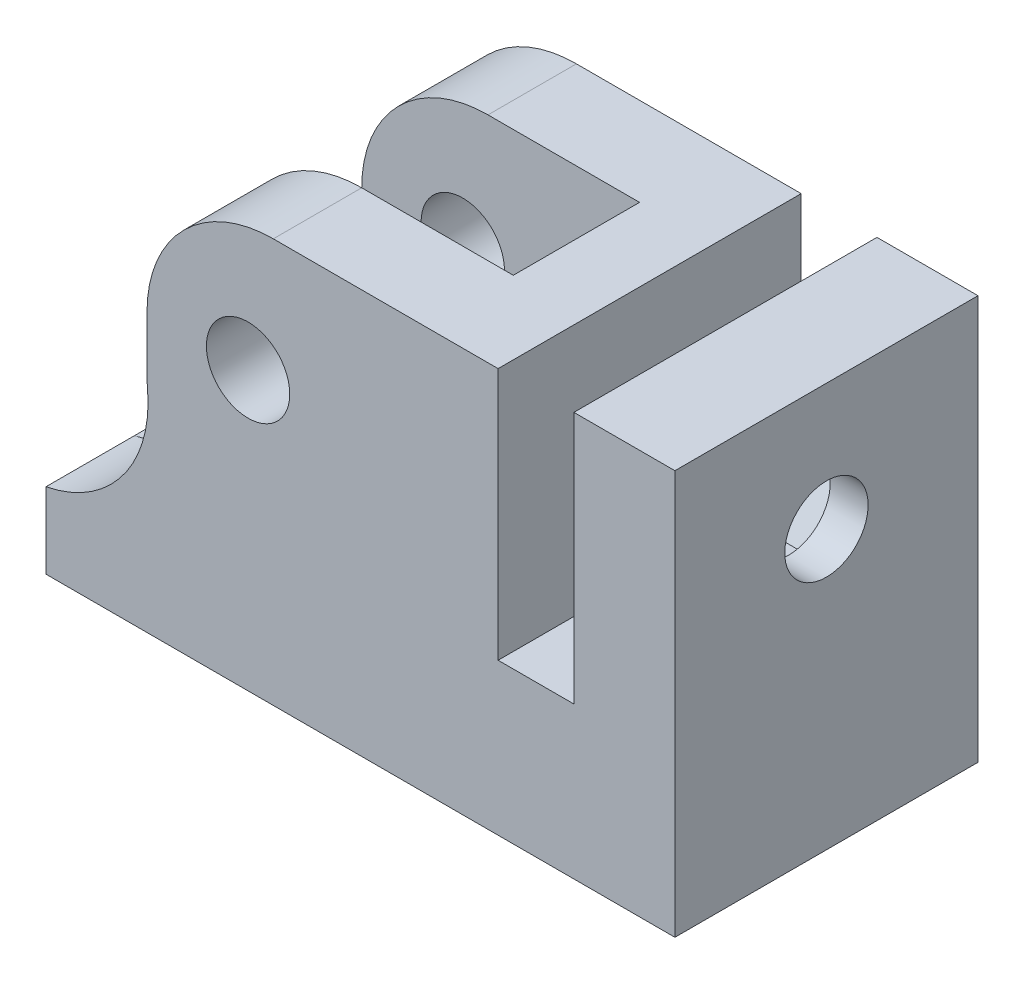
SolidWorks part; units mm, degrees
ref_plane "Plano frontal" through (0, 0, 0) normal (0, 0, 1) x (1, 0, 0)
ref_plane "Plano superior" through (0, 0, 0) normal (0, 1, 0) x (1, 0, 0)
ref_plane "Plano direito" through (0, 0, 0) normal (1, 0, 0) x (0, 0, -1)
sketch "Esboço1" plane through (0, 0, 0) normal (0, 0, 1) x (1, 0, 0)
  line L0 (0, 0) -> (-13.9, 0)
  line L1 (-13.9, 0) -> (-13.9, -10)
  line L3 (-13.9, -10) -> (-4, -16)
  line L4 (-4, -16) -> (7, -16)
  line L5 (7, -16) -> (7, 0)
  line L6 (7, 0) -> (3, 0)
  line L7 (3, 0) -> (3, -10)
  line L8 (3, -10) -> (0, -10)
  line L9 (0, -10) -> (0, 0)
  circle A0 centre (-9.9, -5) radius 1.65
  circle A1 centre (-9.9, -5) radius 6 construction
  point P3 (1.5, -10)
  point P5 (0, -5)
  dimension "D8" = 3.3
  dimension "D9" = 12
  dimension "D2" = 4
  dimension "D3" = 10
  dimension "D4" = 3
  dimension "D5" = 4
  dimension "D6" = 6
  dimension "D7" = 11.4
  dimension "D1" = 4
extrude "Ressalto-extrusão1" add sketch "Esboço1" along normal blind 12
sketch "Esboço2" plane through (0, 0, 0) normal (0, 1, 0) x (1, 0, 0)
  line L1 (-13.9, -3.5) -> (-2.9, -3.5)
  line L2 (-13.9, -3.5) -> (-13.9, -8.5)
  line L3 (-13.9, -8.5) -> (-2.9, -8.5)
  line L4 (-2.9, -3.5) -> (-2.9, -8.5)
  line L5 (-13.9, -3.5) -> (-2.9, -8.5) construction
  line L6 (-13.9, -8.5) -> (-2.9, -3.5) construction
  line L7 (-8.25, 0) -> (-11.55, 0) construction
  line L8 (-8.25, 0) -> (-11.55, 0) construction
  line L9 (-13.9, -12) -> (-13.9, 0) construction
  point P0 (-8.4, -6)
  point P5 (-13.9, -3.1033)
  point P9 (-9.9, 0)
  point P11 (-13.9, -7.0902)
  point P12 (-13.9, -6)
  point P13 (-13.9, -3.8508)
  dimension "D1" = 7
  dimension "D2" = 5
extrude "Corte-extrusão1" cut sketch "Esboço2" against normal through all
fillet "Filete1" radius 5 5 edges at (-4, -16, 1.75) (-13.9, -10, 10.25) (-13.9, -10, 1.75) (-13.9, 0, 1.75) (-13.9, 0, 10.25)
sketch "Esboço3" plane through (3, 0, 0) normal (-1, 0, 0) x (0, 0, 1)
  line L0 (0, 0) -> (0, -10) construction
  line L1 (2.5359, -5) -> (4.2679, -8)
  line L2 (4.2679, -8) -> (7.7321, -8)
  line L3 (7.7321, -8) -> (9.4641, -5)
  line L4 (9.4641, -5) -> (7.7321, -2)
  line L5 (7.7321, -2) -> (4.2679, -2)
  line L6 (4.2679, -2) -> (2.5359, -5)
  line L8 (12, 0) -> (0, 0) construction
  circle A0 centre (6, -5) radius 3 construction
  circle A1 centre (6, -5) radius 1.65
  point P11 (0, -5)
  point P17 (6, 0)
  dimension "D1" = 6
  dimension "D2" = 3.3
extrude "Corte-extrusão2" cut sketch "Esboço3" against normal blind 2.5
extrude "Corte-extrusão3" cut sketch "Esboço3<2>" against normal through all contours A1 region at (3, -5, 6)
sketch "Esboço3<2>" plane through (3, 0, 0) normal (-1, 0, 0) x (0, 0, 1) same geometry as "Esboço3"
sketch "Esboço4" plane through (0, -16, 0) normal (0, -1, 0) x (1, 0, 0)
  line L0 (7, 12) -> (-17.9, 12)
  line L1 (-17.9, 12) -> (-17.9, 0)
  line L2 (-17.9, 0) -> (-14.4, 0)
  line L3 (-11.4915, 0) -> (-5.1946, 0) construction
  line L4 (-14.4, 0) -> (-14.4, 4.5)
  line L7 (-14.4, 7.5) -> (-5.4, 7.5)
  line L10 (-5.4, 4.5) -> (-5.4, 0)
  line L11 (-5.1946, 0) -> (-2.6031, 0) construction
  line L12 (-5.4, 0) -> (7, 0)
  line L13 (7, 0) -> (7, 12)
  line L14 (-11.55, 0) -> (-8.25, 0) construction
  line L15 (-11.55, 0) -> (-8.25, 0) construction
  line L16 (-9.9, 0) -> (-9.9, 12.723) construction
  line L17 (-2.9, 3.5) -> (-2.9, 8.5) construction
  arc A0 (-14.4, 4.5) -> (-14.4, 7.5) centre (-14.4, 6) cw
  arc A1 (-5.4, 7.5) -> (-5.4, 4.5) centre (-5.4, 6) cw
  point P0 (-9.9, 0)
  point P11 (0, 0)
  point P15 (-2.9, 6)
  dimension "D2" = 2
  dimension "D3" = 1.5
  dimension "D1" = 9
extrude "Ressalto-extrusão2" add sketch "Esboço4" against normal blind 3
fillet "Filete2" radius 5 1 edges at (-8.95, -13, 10.25)
equation "\"D5@Esboço1\"=\"D2@Esboço1\""
